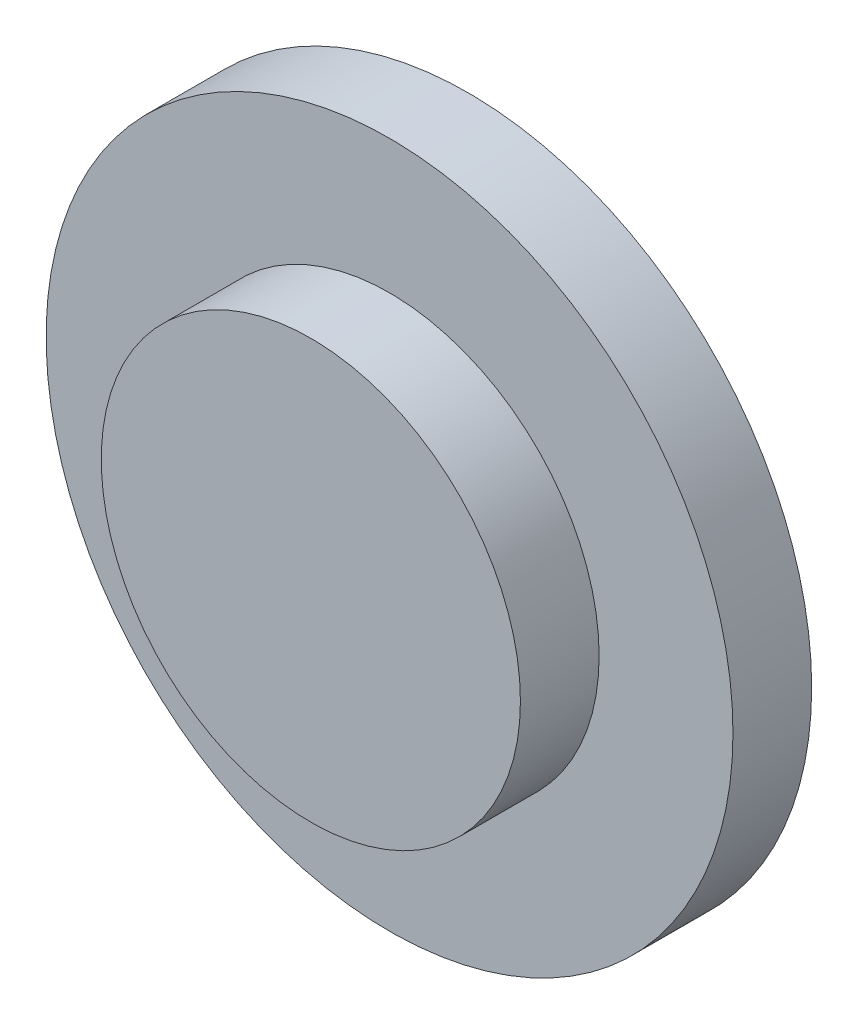
SolidWorks part; units mm, degrees
ref_plane "Front Plane" through (0, 0, 0) normal (0, 0, 1) x (1, 0, 0)
ref_plane "Top Plane" through (0, 0, 0) normal (0, 1, 0) x (1, 0, 0)
ref_plane "Right Plane" through (0, 0, 0) normal (1, 0, 0) x (0, 0, -1)
sketch "Sketch1" plane through (0, 0, 0) normal (0, 0, 1) x (1, 0, 0)
  circle A0 centre (0, 0) radius 43.6326
extrude "Boss-Extrude1" add sketch "Sketch1" along normal blind 10
sketch "Sketch2" plane through (0, 0, 10) normal (0, 0, 1) x (1, 0, 0)
  circle A0 centre (0, 0) radius 18.0827
extrude "Cut-Extrude1" cut sketch "Sketch2" against normal up to surface (10 mm away) up to face at (43.6326, 0, 0)
sketch "Sketch3" plane through (0, 0, 10) normal (0, 0, 1) x (1, 0, 0)
  circle A0 centre (0, 0) radius 26.6286
extrude "Boss-Extrude2" add sketch "Sketch3" along normal blind 10
